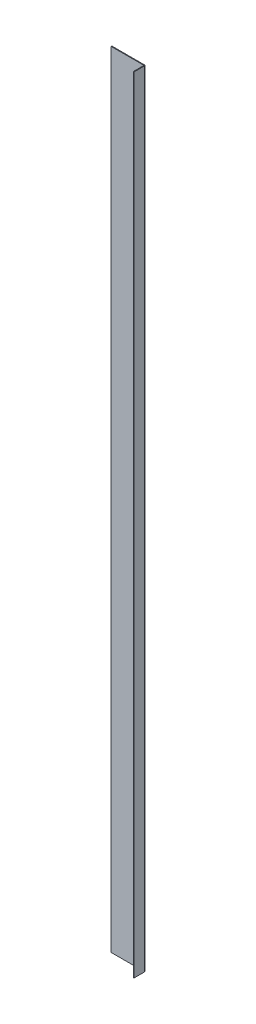
SolidWorks part; units mm, degrees
note: The reader was unsure of these and kept them because the rebuilt part matched: flange length of "Odgięcie krawędzi1".
material "AISI 304"
ref_plane "Płaszczyzna przednia" through (0, 0, 0) normal (0, 0, 1) x (1, 0, 0)
ref_plane "Płaszczyzna górna" through (0, 0, 0) normal (0, 1, 0) x (1, 0, 0)
ref_plane "Płaszczyzna prawa" through (0, 0, 0) normal (1, 0, 0) x (0, 0, -1)
sketch "Szkic1" plane through (0, 0, 0) normal (0, 0, 1) x (1, 0, 0)
  line L0 (0, 0) -> (0, 2270)
  line L1 (0, 2270) -> (95, 2270)
  line L3 (95, 0) -> (0, 0)
  line L5 (95, 0) -> (95, 2270)
  dimension "D1" = 2270
  dimension "D2" = 95
base flange "Odgięcie bazowe1" sketch "Szkic1" thickness 2 reverse thickness direction no parameters "D1"=0.7366
edge flange "Odgięcie krawędzi1" sketch "Szkic13" flange angle 90 flange length 32.74 flange position material outside bend radius 0.7366 thickness 2 relief rectangular parameters "D6"=10
sketch "Szkic13" plane through (95, 0, 0) normal (1, 0, 0) x (0, 1, 0)
  line L0 (0, 0) -> (2270, 0) construction
  line L1 (0, 0) -> (2270, 0)
  line L2 (0, 0) -> (0, 30.74)
  line L3 (0, 30.74) -> (2270, 30.74)
  line L4 (2270, 30.74) -> (2270, 0)
bend "Zgięcie krawędziowe1" bend radius 0.7366 bend angle 90 parameters "D5"=1
sketch "Linie zgięcia1" [suppressed] plane through (0, 0, 0) normal (0, 1, 0) x (1, 0, 0)
sketch "Ramka-graniczna1" [suppressed] plane through (0, 0, 0) normal (0, 1, 0) x (1, 0, 0)
sheet metal parameters "Arkusz blachy1" thickness 2 parameters "D1"=0.7366
flat pattern "Rozłożony model1" [suppressed]
sketch "Linie zgięcia2" plane through (0, 0, 0) normal (0, 1, 0) x (1, 0, 0)
sketch3d "Ramka-graniczna2" [suppressed]
  line L0 (81.5, 2310, 0) -> (81.5, 0, 0) construction
  line L1 (0, 2310, 0) -> (0, 0, 0) construction
  line L2 (81.5, 2310, 0) -> (0, 2310, 0) construction
  line L3 (81.5, 0, 0) -> (0, 0, 0) construction
sheet metal parameters "Arkusz blachy3" thickness 2 parameters "D1"=0.7366
flat pattern "Rozłożony model1"
sketch "Linie zgięcia2" plane through (0, 0, 0) normal (0, 0, 1) x (1, 0, 0)
  line L0 (95.6273, 0) -> (95.6273, 2270) construction
  line L1 (95.6273, 0) -> (95.6273, 2270) construction
sketch3d "Ramka-graniczna2" [suppressed]
  line L0 (126.9946, 2270, 0) -> (126.9946, 0, 0) construction
  line L1 (0, 2270, 0) -> (0, 0, 0) construction
  line L2 (126.9946, 2270, 0) -> (0, 2270, 0) construction
  line L3 (126.9946, 0, 0) -> (0, 0, 0) construction
bend of the flat pattern "Rozłożone-<Zgięcie krawędziowe1>1"
